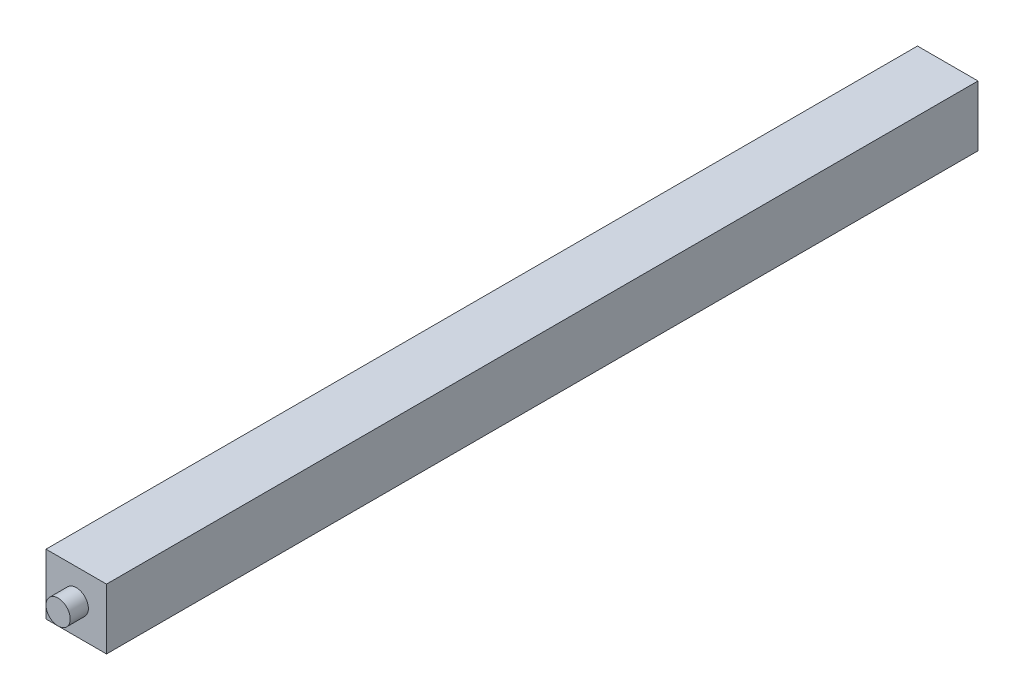
SolidWorks part; units mm, degrees
ref_plane "前视基准面" through (0, 0, 0) normal (0, 0, 1) x (1, 0, 0)
ref_plane "上视基准面" through (0, 0, 0) normal (0, 1, 0) x (1, 0, 0)
ref_plane "右视基准面" through (0, 0, 0) normal (1, 0, 0) x (0, 0, -1)
other "Configuration Table"
sketch "Sketch1" plane through (0, 0, 0) normal (0, 0, 1) x (1, 0, 0)
  line L1 (-25, -25) -> (25, -25)
  line L2 (-25, -25) -> (-25, 25)
  line L3 (-25, 25) -> (25, 25)
  line L4 (25, -25) -> (25, 25)
  line L5 (-25, -25) -> (25, 25) construction
  line L6 (-25, 25) -> (25, -25) construction
  point P0 (0, 0)
extrude "Boss-Extrude1" add sketch "Sketch1" along normal blind 720
ref_plane "Plane1" through (0, 0, 720) normal (0, 0, 1) x (1, 0, 0)
sketch "Sketch2" plane through (0, 0, 720) normal (0, 0, 1) x (1, 0, 0)
  circle A0 centre (0, 0) radius 10
extrude "Boss-Extrude2" add sketch "Sketch2" along normal blind 15
sketch3d "3DSketch1"
  line L0 (0, 0, 0) -> (0, 0, 735) construction
ref_axis "boss_axis" through (0, 0, 0) along (0, 0, 1)
ref_plane "leg_top_face" through (0, 0, 720) normal (0, 0, 1) x (1, 0, 0)
ref_plane "leg_bottom_face" through (0, 0, 0) normal (0, 0, 1) x (1, 0, 0)
